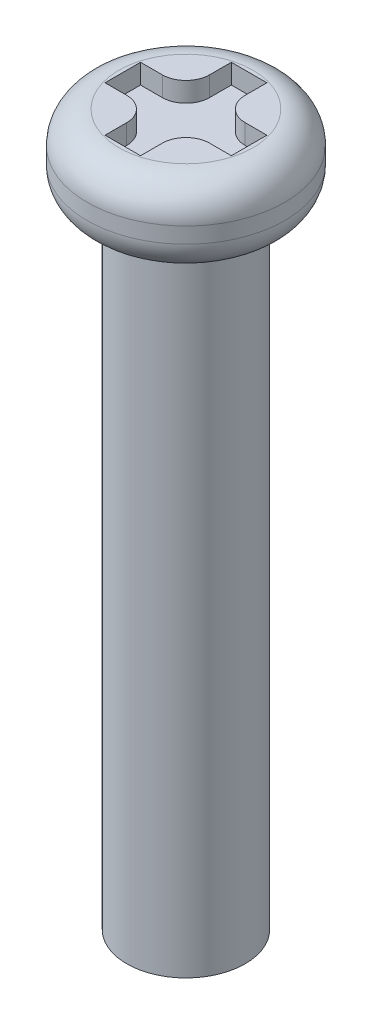
SolidWorks part; units mm, degrees
ref_plane "Front Plane" through (0, 0, 0) normal (0, 0, 1) x (1, 0, 0)
ref_plane "Top Plane" through (0, 0, 0) normal (0, 1, 0) x (1, 0, 0)
ref_plane "Right Plane" through (0, 0, 0) normal (1, 0, 0) x (0, 0, -1)
sketch "Sketch1" plane through (0, 0, 0) normal (1, 0, 0) x (0, 0, -1)
  line L1 (0, 0) -> (2.5, 0)
  line L2 (0, 0) -> (0, 2)
  line L3 (0, 2) -> (2.5, 2)
  line L4 (2.5, 0) -> (2.5, 2)
  arc A0 (2.5, 0) -> (0.5, 2) centre (0.5, 0) ccw
  dimension "D1" = 2.5
  dimension "D2" = 2
revolve "Revolve1" add sketch "Sketch1" angle 360 about L2 region at (0, 0.8853, -1.0835) region at (0, 1.5533, -2.0533)
fillet "Fillet2" radius 0.8 2 edges at (0, 0, -2.5) (0, 2, -2.5)
sketch "Sketch3" plane through (0, 2, 0) normal (0, 1, 0) x (1, 0, 0)
  line L1 (0.45, -1.6) -> (-0.45, -1.6)
  line L2 (0.45, -1.6) -> (0.45, 1.6)
  line L3 (0.45, 1.6) -> (-0.45, 1.6)
  line L4 (-0.45, -1.6) -> (-0.45, 1.6)
  line L5 (0.45, -1.6) -> (-0.45, 1.6) construction
  line L6 (0.45, 1.6) -> (-0.45, -1.6) construction
  point P0 (0, 0)
  dimension "D1" = 0.9
  dimension "D2" = 3.2
extrude "Cut-Extrude1" cut sketch "Sketch3" against normal blind 0.5 contours L2 L3 L4 L1
sketch "Sketch4" plane through (0, 1.5, 0) normal (0, 1, 0) x (1, 0, 0)
  line L0 (-0.45, 1.6) -> (0.45, 1.6) construction
  line L1 (-1.6, -0.45) -> (1.6, -0.45)
  line L2 (-1.6, -0.45) -> (-1.6, 0.45)
  line L3 (-1.6, 0.45) -> (1.6, 0.45)
  line L4 (1.6, -0.45) -> (1.6, 0.45)
  line L5 (-1.6, -0.45) -> (1.6, 0.45) construction
  line L6 (-1.6, 0.45) -> (1.6, -0.45) construction
  line L7 (0.45, 1.6) -> (-0.45, 1.6) construction
  line L8 (-0.45, -1.6) -> (-0.45, 1.6) construction
  point P0 (0, 0)
  dimension "D1" = 3.2
extrude "Cut-Extrude2" cut sketch "Sketch4" along normal through all
fillet "Fillet1" radius 0.6 4 edges at (0.45, 1.75, 0.45) (-0.45, 1.75, 0.45) (0.45, 1.75, -0.45) (-0.45, 1.75, -0.45)
sketch "Sketch2" plane through (0, 0, 0) normal (0, -1, 0) x (1, 0, 0)
  circle A0 centre (0, 0) radius 1.5
  dimension "D1" = 3
extrude "Boss-Extrude1" add sketch "Sketch2" along normal blind 16
